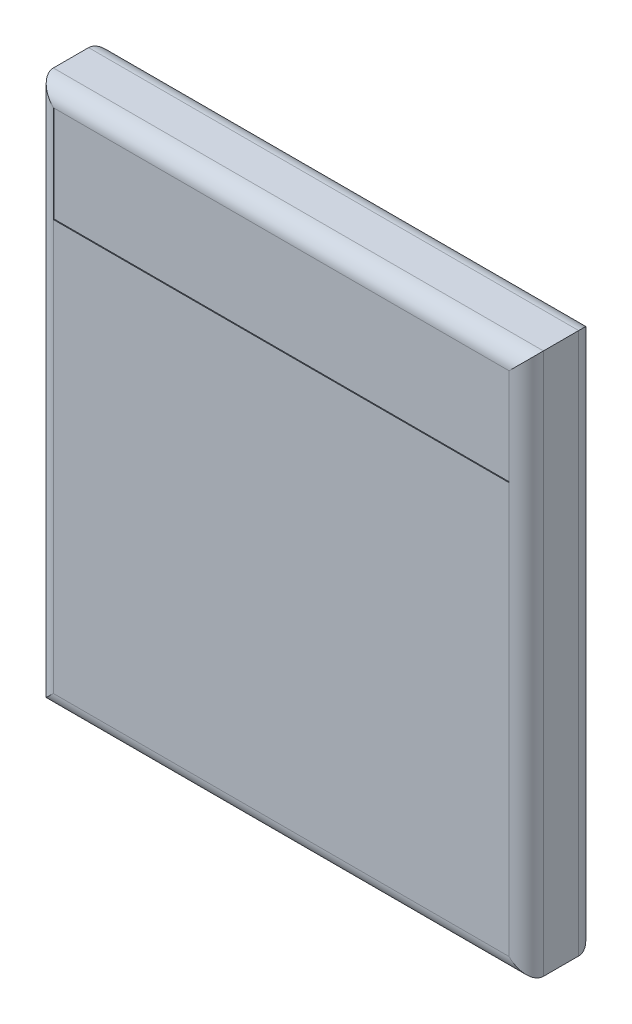
SolidWorks part; units mm, degrees
material "Alliage 1060"
ref_plane "Plan de face" through (0, 0, 0) normal (0, 0, 1) x (1, 0, 0)
ref_plane "Plan de dessus" through (0, 0, 0) normal (0, 1, 0) x (1, 0, 0)
ref_plane "Plan de droite" through (0, 0, 0) normal (1, 0, 0) x (0, 0, -1)
sketch "Esquisse1" plane through (0, 0, 0) normal (0, 0, 1) x (1, 0, 0)
  line L1 (-28.5, -31.5) -> (28.5, -31.5)
  line L2 (-28.5, -31.5) -> (-28.5, 31.5)
  line L3 (-28.5, 31.5) -> (28.5, 31.5)
  line L4 (28.5, -31.5) -> (28.5, 31.5)
  line L5 (-28.5, -31.5) -> (28.5, 31.5) construction
  line L6 (-28.5, 31.5) -> (28.5, -31.5) construction
  point P0 (0, 0)
  dimension "D1" = 57
  dimension "D2" = 63
extrude "Boss.-Extru.1" add sketch "Esquisse1" along normal blind 4.05 and the other way blind 4.05
fillet "Congé1" radius 2 8 edges at (0, -31.5, -4.05) (28.5, 0, -4.05) (-28.5, 0, -4.05) (0, -31.5, 4.05) (-28.5, 0, 4.05) (28.5, 0, 4.05) (0, 31.5, -4.05) (0, 31.5, 4.05)
sketch "Esquisse3" plane through (0, 0, -4.05) normal (0, 0, -1) x (-1, 0, 0)
  line L0 (26.5, -29.5) -> (26.5, 29.5) construction
  line L1 (-26.5, 29.5) -> (26.5, 29.5)
  line L2 (-26.5, 29.5) -> (-26.5, 18.231)
  line L3 (-26.5, 18.231) -> (26.5, 18.231)
  line L4 (26.5, 29.5) -> (26.5, 18.231)
extrude "Enlèv. mat.-Extru.1" cut sketch "Esquisse3" against normal blind 0.1
sketch "Esquisse4" plane through (0, 0, 4.05) normal (0, 0, 1) x (1, 0, 0)
  line L1 (-26.5, 29.5) -> (26.5, 29.5)
  line L2 (-26.5, 29.5) -> (-26.5, 18.231)
  line L3 (-26.5, 18.231) -> (26.5, 18.231)
  line L4 (26.5, 29.5) -> (26.5, 18.231)
extrude "Enlèv. mat.-Extru.2" cut sketch "Esquisse4" against normal blind 0.1
sketch "Esquisse5" plane through (0, 0, -4.05) normal (0, 0, -1) x (-1, 0, 0)
  text T0 "3000 mAh"
extrude "Enlèv. mat.-Extru.3" cut sketch "Esquisse5" against normal blind 0.1
